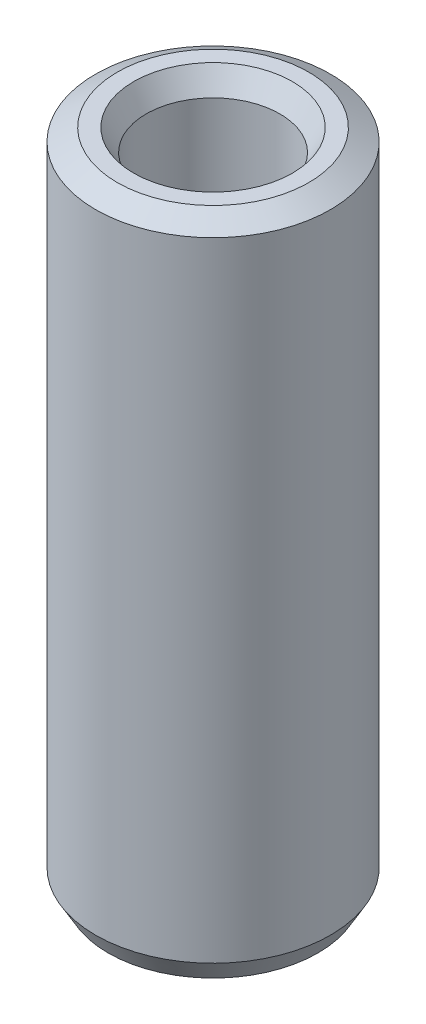
SolidWorks part; units mm, degrees
ref_plane "Front Plane" through (0, 0, 0) normal (0, 0, 1) x (1, 0, 0)
ref_plane "Top Plane" through (0, 0, 0) normal (0, 1, 0) x (1, 0, 0)
ref_plane "Right Plane" through (0, 0, 0) normal (1, 0, 0) x (0, 0, -1)
sketch "Sketch1" plane through (0, 0, 0) normal (0, 1, 0) x (1, 0, 0)
  circle A0 centre (0, 0) radius 20
  dimension "SLEEVE_OD" = 40
extrude "Boss-Extrude1" add sketch "Sketch1" along normal blind 112.8317
sketch "Sketch2" plane through (0, 0, 0) normal (0, 1, 0) x (1, 0, 0)
  circle A0 centre (0, 0) radius 11.38
  dimension "BORE_D" = 22.76
extrude "Cut-Extrude1" cut sketch "Sketch2" along normal through all
chamfer "Chamfer1" distance 2.1346 angle 60 4 edges at (0, 112.8317, 11.38) (0, 0, 11.38) (0, 0, 20) (0, 112.8317, 20) first distance on face at (0, 112.8317, 11.38) first distance on face at (0, 0, 11.38) first distance on face at (0, 112.8317, 20)
